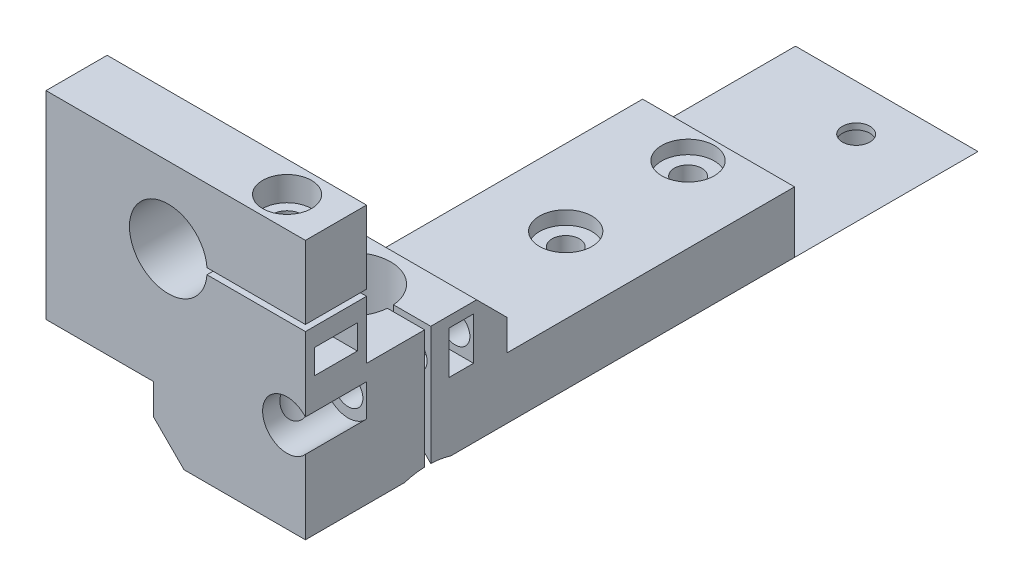
SolidWorks part; units mm, degrees
ref_plane "Front Plane" through (0, 0, 0) normal (0, 0, 1) x (1, 0, 0)
ref_plane "Top Plane" through (0, 0, 0) normal (0, 1, 0) x (1, 0, 0)
ref_plane "Right Plane" through (0, 0, 0) normal (1, 0, 0) x (0, 0, -1)
sketch "Sketch1" plane through (0, 0, 0) normal (0, 1, 0) x (1, 0, 0)
  line L1 (-12.425, 55) -> (12.425, 55)
  line L2 (-12.425, 55) -> (-12.425, -55)
  line L3 (-12.425, -55) -> (12.425, -55)
  line L4 (12.425, 55) -> (12.425, -55)
  line L5 (-12.425, 55) -> (12.425, -55) construction
  line L6 (-12.425, -55) -> (12.425, 55) construction
  point P0 (0, 0)
  dimension "D1" = 24.85
  dimension "D2" = 110
extrude "Boss-Extrude1" add sketch "Sketch1" along normal blind 15
sketch "Sketch2" plane through (0, 15, 0) normal (0, 1, 0) x (1, 0, 0)
  line L0 (12.425, -55) -> (12.425, 55) construction
  line L1 (-12.425, 55) -> (12.425, 55)
  line L2 (-12.425, 55) -> (-12.425, 25)
  line L3 (-12.425, 25) -> (12.425, 25)
  line L4 (12.425, 55) -> (12.425, 25)
  dimension "D1" = 30
extrude "Cut-Extrude1" cut sketch "Sketch2" against normal blind 10
sketch "Sketch3" plane through (0, 15, 0) normal (0, 1, 0) x (1, 0, 0)
  line L0 (12.425, -55) -> (12.425, 25) construction
  line L1 (12.425, -20) -> (2.425, -20)
  line L2 (12.425, -20) -> (12.425, 10)
  line L3 (12.425, 10) -> (2.425, 10)
  line L4 (2.425, -20) -> (2.425, 10)
  line L5 (-12.425, 25) -> (12.425, 25) construction
  dimension "D1" = 30
  dimension "D2" = 10
  dimension "D3" = 15
extrude "Cut-Extrude2" [suppressed] cut sketch "Sketch3" against normal through all
sketch "Sketch4" plane through (-12.425, 0, 0) normal (-1, 0, 0) x (0, 0, 1)
  line L1 (55, 0) -> (20, 0)
  line L2 (55, 0) -> (55, 5)
  line L3 (55, 5) -> (20, 5)
  line L4 (20, 0) -> (20, 5)
  dimension "D1" = 5
  dimension "D2" = 35
extrude "Cut-Extrude3" cut sketch "Sketch4" against normal through all
sketch "Sketch5" plane through (0, 15, 0) normal (0, 1, 0) x (1, 0, 0)
  line L1 (-12.425, -55) -> (-30, -55)
  line L2 (-12.425, -55) -> (-12.425, -44)
  line L3 (-12.425, -44) -> (-30, -44)
  line L4 (-30, -55) -> (-30, -44)
  dimension "D1" = 11
  dimension "D2" = 30
extrude "Boss-Extrude2" add sketch "Sketch5" against normal up to surface (10 mm away) up to face at (0, 5, 37.5)
sketch "Sketch6" plane through (0, 15, 0) normal (0, 1, 0) x (1, 0, 0)
  line L0 (-30, -44) -> (-30, -55) construction
  line L1 (12.425, -55) -> (-30, -55)
  line L2 (12.425, -55) -> (12.425, -45)
  line L3 (12.425, -45) -> (-30, -45)
  line L4 (-30, -55) -> (-30, -45)
  dimension "D1" = 10
extrude "Boss-Extrude3" add sketch "Sketch6" along normal blind 32.42
fillet "Fillet1" [suppressed] radius 10
chamfer "Chamfer2" distance 5 angle 45 2 edges at (12.425, 0, -17.5) (-12.425, 0, -17.5)
sketch "Sketch7" plane through (0, 15, 0) normal (0, 1, 0) x (1, 0, 0)
  circle A0 centre (0, -35) radius 6.35
  dimension "D1" = 12.7
  dimension "D2" = 35
extrude "Cut-Extrude4" cut sketch "Sketch7" against normal through all
sketch "Sketch8" plane through (0, 0, 44) normal (0, 0, -1) x (-1, 0, 0)
  line L0 (-12.425, 5) -> (12.425, 5) construction
  circle A0 centre (10, 35) radius 6.35
  dimension "D1" = 12.7
  dimension "D2" = 30
  dimension "D3" = 10
extrude "Cut-Extrude5" cut sketch "Sketch8" against normal through all
hole_wizard "CBORE for M4 SHCS1" positions "Sketch9" profile "Sketch10" counterbore size "M4" standard "ANSI Metric"
sketch "Sketch9" plane through (0, 0, 0) normal (0, -1, 0) x (-1, 0, 0)
  line L0 (0, 55) -> (0, 47.5) construction
  line L1 (-7.425, 55) -> (7.425, 55) construction
  line L2 (0, 47.5) -> (0, 40) construction
  line L3 (0, 40) -> (0, 32.5) construction
  line L4 (0, 32.5) -> (0, 25) construction
  point P0 (0, 47.5)
  point P2 (0, 32.5)
  dimension "D1" = 30
sketch "Sketch10" plane through (0, 0, -47.5) normal (1, 0, 0) x (0, 0, -1)
  line L0 (0, 0) -> (0, 11.4519)
  line L1 (0, 11.4519) -> (2.25, 10.1)
  line L2 (2.25, 10.1) -> (2.25, 4)
  line L3 (2.25, 4) -> (4, 4)
  line L4 (4, 4) -> (4, 0)
  line L5 (4, 0) -> (0, 0)
  line L10 (0, 11.4519) -> (-2.25, 10.1) construction
  line L11 (0, -6.35) -> (0, 107.95) construction
  dimension "Hole Dia." = 4.5
  dimension "Hole Depth" = 10.1
  dimension "C'Bore Dia." = 8
  dimension "C'Bore Depth" = 4
  dimension "Drill Angle" = 118
hole_wizard "M4x0.7 Tapped Hole1" positions "Sketch13" profile "Sketch14" tap size "M4x0.7" standard "ANSI Metric" end condition through all
sketch "Sketch13" plane through (0, 0, 0) normal (0, -1, 0) x (-1, 0, 0)
  line L0 (-7.425, 55) -> (7.425, 55) construction
  point P0 (0, 20)
  point P2 (0, 0)
  dimension "D1" = 20
  dimension "D2" = 35
sketch "Sketch14" plane through (0, 0, -20) normal (1, 0, 0) x (0, 0, -1)
  line L0 (0, 0) -> (0, 47.42)
  line L1 (0, 47.42) -> (1.65, 47.42)
  line L2 (1.65, 47.42) -> (1.65, 0)
  line L5 (1.65, 0) -> (0, 0)
  line L11 (0, -6.35) -> (0, 107.95) construction
  dimension "Thru Tap Drill Dia." = 3.3
  dimension "Thru Tap Drill Depth" = 47.42
cosmetic thread "Hole Thread1" parameters "D2"=4
cosmetic thread "Hole Thread2" parameters "D2"=4
sketch "Sketch15" plane through (0, 0, 44) normal (0, 0, -1) x (-1, 0, 0)
  line L0 (30, 5) -> (30, 15) construction
  line L1 (12.425, 5) -> (30, 5)
  line L2 (12.425, 5) -> (12.425, 15)
  line L3 (12.425, 15) -> (30, 15)
  line L4 (30, 5) -> (30, 15)
extrude "Cut-Extrude6" cut sketch "Sketch15" against normal through all
chamfer "Chamfer6" distance 5 angle 45 1 edges at (-12.425, 5, 37.5)
sketch "Sketch16" plane through (0, 15, 0) normal (0, 1, 0) x (1, 0, 0)
  line L0 (0, -35) -> (12.425, -35) construction
  line L1 (12.425, -45) -> (12.425, 25) construction
  line L3 (4.925, -34.5) -> (19.925, -34.5)
  line L4 (4.925, -34.5) -> (4.925, -35.5)
  line L5 (4.925, -35.5) -> (19.925, -35.5)
  line L6 (19.925, -34.5) -> (19.925, -35.5)
  line L7 (4.925, -34.5) -> (19.925, -35.5) construction
  line L8 (4.925, -35.5) -> (19.925, -34.5) construction
  dimension "D1" = 1
  dimension "D2" = 15
extrude "Cut-Extrude7" cut sketch "Sketch16" against normal through all
sketch "Sketch17" plane through (0, 0, 55) normal (0, 0, 1) x (1, 0, 0)
  line L1 (12.425, 15) -> (6.3303, 15) construction
  line L2 (12.425, 15) -> (12.425, 5) construction
  line L3 (12.425, 5) -> (6.3303, 5) construction
  line L4 (6.3303, 15) -> (6.3303, 5) construction
sketch "Sketch24" plane through (0, 0, 55) normal (0, 0, 1) x (1, 0, 0)
  line L0 (-10, 35) -> (12.425, 35) construction
  line L1 (12.425, 47.42) -> (12.425, 11.3914) construction
  line L3 (-9.575, 35.5) -> (12.425, 35.5)
  line L4 (-9.575, 35.5) -> (-9.575, 34.5)
  line L5 (-9.575, 34.5) -> (12.425, 34.5)
  line L6 (12.425, 35.5) -> (12.425, 34.5)
  line L7 (-9.575, 35.5) -> (12.425, 34.5) construction
  line L8 (-9.575, 34.5) -> (12.425, 35.5) construction
  point P5 (1.425, 35)
  dimension "D1" = 1
  dimension "D2" = 22
extrude "Cut-Extrude8" cut sketch "Sketch24" against normal up to next
hole_wizard "CBORE for M4 SBHCS1" positions "Sketch35" profile "Sketch36" counterbore size "M4" standard "ANSI Metric" end condition through all
sketch "Sketch35" plane through (0, 15, 0) normal (0, 1, 0) x (1, 0, 0)
  point P0 (0, 20)
  point P3 (0, 0)
sketch "Sketch36" plane through (0, 15, -20) normal (1, 0, 0) x (0, 0, 1)
  line L0 (0, 0) -> (0, 15)
  line L1 (0, 15) -> (2.25, 15)
  line L3 (2.25, 15) -> (2.25, 2.2)
  line L4 (2.25, 2.2) -> (4.3, 2.2)
  line L5 (4.3, 2.2) -> (4.3, 0)
  line L7 (4.3, 0) -> (0, 0)
  line L11 (0, -6.35) -> (0, 107.95) construction
  dimension "Thru Hole Dia." = 4.5
  dimension "Thru Hole Depth" = 15
  dimension "C'Bore Dia." = 8.6
  dimension "C'Bore Depth" = 2.2
sketch "Sketch37" plane through (0, 15, 0) normal (0, 1, 0) x (1, 0, 0)
  line L5 (12.425, -35.5) -> (6.3303, -35.5)
  line L7 (12.425, -35.5) -> (6.3303, -35.5)
  line L9 (12.425, -34.5) -> (12.425, 25)
  line L10 (12.425, 25) -> (-12.425, 25)
  line L11 (-12.425, 25) -> (-12.425, -45)
  line L16 (12.425, -34.5) -> (12.425, -22)
  line L17 (12.425, -22) -> (-12.425, -22)
  line L18 (-12.425, -22) -> (-12.425, -45)
  line L21 (6.3303, -34.5) -> (12.425, -34.5)
  line L22 (6.3303, -34.5) -> (12.425, -34.5)
  line L23 (-12.425, -45) -> (12.425, -45)
  line L25 (12.425, -45) -> (12.425, -35.5)
  line L26 (12.425, -45) -> (12.425, -35.5)
  line L27 (-12.425, -45) -> (12.425, -45)
  arc A1 (6.3303, -34.5) -> (6.3303, -35.5) centre (0, -35) ccw
  arc A3 (6.3303, -34.5) -> (6.3303, -35.5) centre (0, -35) ccw
  dimension "D2" = 23
  dimension "D1" = 0
extrude "Boss-Extrude4" add sketch "Sketch37" along normal blind 10
sketch "Sketch38" plane through (0, 5, 0) normal (0, -1, 0) x (1, 0, 0)
  circle A0 centre (0, 35) radius 10
  dimension "D1" = 20
extrude "Cut-Extrude10" cut sketch "Sketch38" against normal blind 10
chamfer "Chamfer7" distance 3 angle 45 1 edges at (3.3536, 5, 25.5791)
chamfer "Chamfer8" distance 5 angle 45 1 edges at (0, 25, 22)
chamfer "Chamfer9" distance 5 angle 45 1 edges at (-12.425, 17.5, 22)
hole_wizard "CBORE for M4 SHCS2" positions "Sketch40" profile "Sketch41" counterbore size "M4" standard "ANSI Metric" end condition through all
sketch "Sketch40" plane through (0, 47.42, 0) normal (0, 1, 0) x (1, 0, 0)
  line L0 (4.425, -45) -> (4.425, -55) construction
  line L1 (12.425, -45) -> (-30, -45) construction
  line L2 (-30, -55) -> (12.425, -55) construction
  line L4 (12.425, -55) -> (12.425, -45) construction
  point P0 (4.425, -50)
  dimension "D1" = 8
sketch "Sketch41" plane through (4.425, 47.42, 50) normal (1, 0, 0) x (0, 0, 1)
  line L0 (0, 0) -> (0, 47.42)
  line L1 (0, 47.42) -> (2.4, 47.42)
  line L3 (2.4, 47.42) -> (2.4, 4)
  line L4 (2.4, 4) -> (4, 4)
  line L5 (4, 4) -> (4, 0)
  line L7 (4, 0) -> (0, 0)
  line L11 (0, -6.35) -> (0, 107.95) construction
  dimension "Thru Hole Dia." = 4.8
  dimension "Thru Hole Depth" = 47.42
  dimension "C'Bore Dia." = 8
  dimension "C'Bore Depth" = 4
hole_wizard "CBORE for M4 SHCS4" positions "Sketch42" profile "Sketch43" counterbore size "M4" standard "ANSI Metric" end condition through all
sketch "Sketch42" plane through (0, 0, 55) normal (0, 0, 1) x (1, 0, 0)
  line L0 (12.425, 34.5) -> (12.425, 5) construction
  point P0 (9.425, 19.7543)
  point P5 (13.2051, 56.5156)
  dimension "D1" = 3
sketch "Sketch43" plane through (9.425, 19.7543, 55) normal (1, 0, 0) x (0, -1, 0)
  line L0 (0, 0) -> (0, 110)
  line L1 (0, 110) -> (2.4, 110)
  line L3 (2.4, 110) -> (2.4, 10)
  line L4 (2.4, 10) -> (4, 10)
  line L5 (4, 10) -> (4, 0)
  line L7 (4, 0) -> (0, 0)
  line L11 (0, -6.35) -> (0, 107.95) construction
  dimension "Thru Hole Dia." = 4.8
  dimension "Thru Hole Depth" = 110
  dimension "C'Bore Dia." = 8
  dimension "C'Bore Depth" = 10
sketch "Sketch44" plane through (0, 0, -55) normal (0, 0, -1) x (-1, 0, 0)
  line L0 (7.425, 0) -> (12.425, 5)
  line L1 (12.425, 5) -> (17.425, 5)
  line L2 (17.425, 5) -> (17.425, 0)
  line L3 (17.425, 0) -> (7.425, 0)
  dimension "D1" = 10
extrude "Boss-Extrude5" add sketch "Sketch44" against normal blind 46
sketch "Sketch45" plane through (12.425, 0, 0) normal (1, 0, 0) x (0, 0, -1)
  line L0 (-50, 29.5) -> (-50, 34.5) construction
  line L1 (-53.5, 31.5) -> (-46.5, 31.5)
  line L2 (-53.5, 31.5) -> (-53.5, 27.5)
  line L3 (-53.5, 27.5) -> (-46.5, 27.5)
  line L4 (-46.5, 31.5) -> (-46.5, 27.5)
  line L5 (-53.5, 31.5) -> (-46.5, 27.5) construction
  line L6 (-53.5, 27.5) -> (-46.5, 31.5) construction
  line L7 (-45, 34.5) -> (-55, 34.5) construction
  point P0 (-50, 29.5)
  dimension "D1" = 7
  dimension "D2" = 4
  dimension "D3" = 3
extrude "Cut-Extrude11" cut sketch "Sketch45" against normal blind 14
sketch "Sketch46" plane through (12.425, 0, 0) normal (1, 0, 0) x (0, 0, -1)
  line L0 (-45, 19.7543) -> (-29.5, 19.7543) construction
  line L1 (-31.5, 23.2543) -> (-27.5, 23.2543)
  line L2 (-31.5, 23.2543) -> (-31.5, 16.2543)
  line L3 (-31.5, 16.2543) -> (-27.5, 16.2543)
  line L4 (-27.5, 23.2543) -> (-27.5, 16.2543)
  line L5 (-31.5, 23.2543) -> (-27.5, 16.2543) construction
  line L6 (-31.5, 16.2543) -> (-27.5, 23.2543) construction
  line L7 (-45, 22.4001) -> (-45, 17.1086) construction
  line L8 (-34.5, 25) -> (-34.5, 5.5649) construction
  point P0 (-29.5, 19.7543)
  dimension "D1" = 4
  dimension "D2" = 7
  dimension "D3" = 3
extrude "Cut-Extrude12" cut sketch "Sketch46" against normal blind 8
